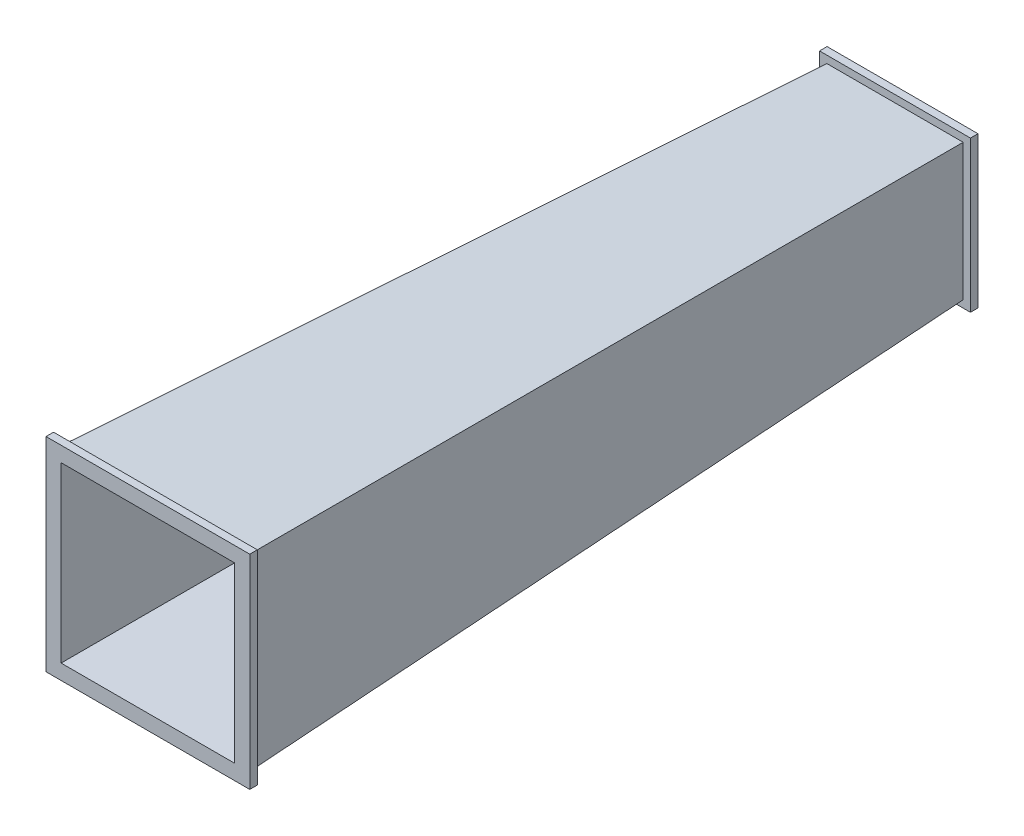
SolidWorks part; units mm, degrees
ref_plane "Front Plane" through (0, 0, 0) normal (0, 0, 1) x (1, 0, 0)
ref_plane "Top Plane" through (0, 0, 0) normal (0, 1, 0) x (1, 0, 0)
ref_plane "Right Plane" through (0, 0, 0) normal (1, 0, 0) x (0, 0, -1)
sketch "Sketch2" plane through (0, 0, 0) normal (0, 0, 1) x (1, 0, 0)
  line L1 (-45, 45) -> (45, 45)
  line L2 (-45, 45) -> (-45, -45)
  line L3 (-45, -45) -> (45, -45)
  line L4 (45, 45) -> (45, -45)
  line L5 (-45, 45) -> (45, -45) construction
  line L6 (-45, -45) -> (45, 45) construction
  point P0 (0, 0)
  dimension "D1" = 90
  dimension "D2" = 90
ref_plane "Plane1" through (0, 0, 500) normal (0, 0, 1) x (1, 0, 0)
sketch "Sketch4" plane through (0, 0, 500) normal (0, 0, 1) x (1, 0, 0)
  line L0 (-45, 45) -> (45, -45) construction
  line L1 (-62.5, 62.5) -> (62.5, 62.5)
  line L2 (-62.5, 62.5) -> (-62.5, -62.5)
  line L3 (-62.5, -62.5) -> (62.5, -62.5)
  line L4 (62.5, 62.5) -> (62.5, -62.5)
  line L5 (-62.5, 62.5) -> (62.5, -62.5) construction
  line L6 (-62.5, -62.5) -> (62.5, 62.5) construction
  point P0 (0, 0)
  dimension "D1" = 125
loft "Loft1" add profiles "Sketch4", "Sketch2" connector at (62.5, 62.5, 500) connector at (45, 45, 0)
shell "Shell3" thickness 5 removed face at (0, 0, 500) removed face at (0, 0, 0)
sketch "Sketch5" plane through (0, 0, 500) normal (0, 0, 1) x (1, 0, 0)
  line L0 (67.5, 67.5) -> (-67.5, 67.5)
  line L1 (-67.5, 67.5) -> (-67.5, -67.5)
  line L2 (-67.5, -67.5) -> (67.5, -67.5)
  line L3 (67.5, -67.5) -> (67.5, 67.5)
  line L4 (62.5, -62.5) -> (62.5, 62.5)
  line L5 (62.5, 62.5) -> (-62.5, 62.5)
  line L6 (-62.5, 62.5) -> (-62.5, -62.5)
  line L7 (-62.5, -62.5) -> (62.5, -62.5)
  line L8 (62.5, -62.5) -> (62.5, 62.5)
  line L9 (62.5, 62.5) -> (-62.5, 62.5)
  line L10 (-62.5, 62.5) -> (-62.5, -62.5)
  line L11 (-62.5, -62.5) -> (62.5, -62.5)
  line M5 (57.4969, 57.4969) -> (57.4969, -57.4969)
  line M6 (57.4969, -57.4969) -> (-57.4969, -57.4969)
  line M7 (-57.4969, -57.4969) -> (-57.4969, 57.4969)
  line M8 (-57.4969, 57.4969) -> (57.4969, 57.4969)
  dimension "D1" = 0
  dimension "D2" = 5
sketch "Sketch6" plane through (0, 0, 0) normal (0, 0, -1) x (-1, 0, 0)
  line L0 (50, 50) -> (-50, 50)
  line L1 (-50, 50) -> (-50, -50)
  line L2 (-50, -50) -> (50, -50)
  line L3 (50, -50) -> (50, 50)
  line L4 (-45, 45) -> (-45, -45)
  line L5 (-45, -45) -> (45, -45)
  line L6 (45, -45) -> (45, 45)
  line L7 (45, 45) -> (-45, 45)
  line L8 (-45, 45) -> (-45, -45)
  line L9 (-45, -45) -> (45, -45)
  line L10 (45, -45) -> (45, 45)
  line L11 (45, 45) -> (-45, 45)
  dimension "D1" = 0
  dimension "D2" = 5
extrude "Boss-Extrude3" add sketch "Sketch6" against normal blind 5
extrude "Boss-Extrude4" add sketch "Sketch5" against normal blind 5 contours L2 L3 L0 L1 | M8 M5 M6 M7 region at (65.5908, 0, 500) region at (0, -60.7322, 500)
